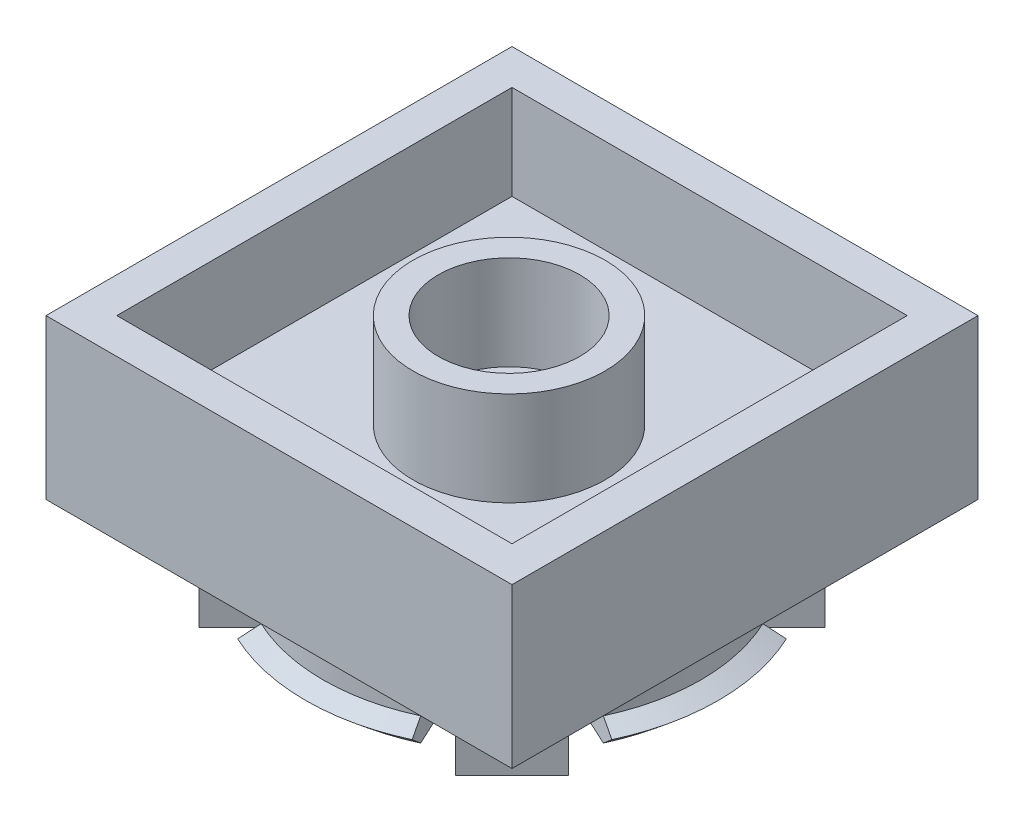
SolidWorks part; units mm, degrees
ref_plane "Front Plane" through (0, 0, 0) normal (0, 0, 1) x (1, 0, 0)
ref_plane "Top Plane" through (0, 0, 0) normal (0, 1, 0) x (1, 0, 0)
ref_plane "Right Plane" through (0, 0, 0) normal (1, 0, 0) x (0, 0, -1)
sketch "Sketch2" plane through (0, 0, 0) normal (0, 1, 0) x (1, 0, 0)
  line L1 (0, 0) -> (15.8, 0)
  line L2 (0, 0) -> (0, 15.8)
  line L3 (0, 15.8) -> (15.8, 15.8)
  line L4 (15.8, 0) -> (15.8, 15.8)
  dimension "D1" = 15.8
  dimension "D2" = 15.8
extrude "Boss-Extrude2" add sketch "Sketch2" against normal blind 5.4
sketch "Sketch4" plane through (0, 0, 0) normal (0, 1, 0) x (1, 0, 0)
  line L0 (15.8, 0) -> (15.8, 15.8) construction
  line L1 (14.6, 14.6) -> (1.2, 14.6)
  line L2 (14.6, 14.6) -> (14.6, 1.2)
  line L3 (14.6, 1.2) -> (1.2, 1.2)
  line L4 (1.2, 14.6) -> (1.2, 1.2)
  line L5 (0, -55) -> (0, 55) construction
  line L6 (-55, 0) -> (55, 0) construction
  line L7 (15.8, 15.8) -> (0, 15.8) construction
  dimension "D1" = 1.2
  dimension "D2" = 1.2
  dimension "D3" = 1.2
  dimension "D4" = 1.2
extrude "Cut-Extrude1" cut sketch "Sketch4" against normal offset from surface (3.2 mm away) 2.2 up to face at (7.9, -5.4, -7.9)
sketch "Sketch7" plane through (0, -3.2, 0) normal (0, 1, 0) x (1, 0, 0)
  line L0 (15.8, 0) -> (15.8, 15.8) construction
  line L1 (15.8, 15.8) -> (0, 15.8) construction
  circle A0 centre (7.85, 7.85) radius 3.255
  circle A1 centre (7.85, 7.85) radius 2.4
  dimension "D1" = 6.51
  dimension "D2" = 4.8
  dimension "D3" = 7.95
  dimension "D4" = 7.95
extrude "Boss-Extrude5" add sketch "Sketch7" along normal up to surface (3.2 mm away) up to face at (7.9, 0, -7.9)
sketch "Sketch8" plane through (0, -5.4, 0) normal (0, -1, 0) x (-1, 0, 0)
  line L0 (-15.8, 0) -> (-15.8, 15.8) construction
  line L1 (-15.8, 15.8) -> (0, 15.8) construction
  circle A0 centre (-7.9, 7.9) radius 5.15
  dimension "D1" = 10.3
  dimension "D2" = 7.9
  dimension "D3" = 7.9
extrude "Cut-Extrude2" cut sketch "Sketch8" against normal blind 0.3
sketch "Sketch11" plane through (0, -5.4, 0) normal (0, -1, 0) x (1, 0, 0)
  line L2 (7.9, -7.9) -> (15.8, 0)
  line L3 (2.97, 0) -> (-2.97, 0) construction
  line L4 (11.683, -2.2078) -> (13.5922, -4.117)
  line L5 (13.5922, -4.117) -> (11.683, -2.2078)
  line L6 (13.5922, -4.117) -> (14.1579, -3.5513)
  line L7 (11.683, -2.2078) -> (12.2487, -1.6421)
  line L8 (14.1579, -3.5513) -> (12.2487, -1.6421)
  line L9 (11.683, -2.2078) -> (10.4597, -3.4311)
  line L10 (13.5922, -4.117) -> (12.3689, -5.3403)
  circle A0 centre (7.9, -7.9) radius 6.7
  circle A1 centre (7.9, -7.9) radius 5.15 construction
  point P9 (12.6376, -3.1624)
  circle M6 centre (7.9, -7.9) radius 5.15
  dimension "D1" = 13.4
  dimension "D2" = 2.7
  dimension "D3" = 0.8
extrude "Boss-Extrude8" add sketch "Sketch11" along normal blind 2.8 contours L2 L8 L7 L4 | A0 L4 L9 | L2 A0 L9 M6 | L10 A0 L2 M6 | A0 L10 L4 | L6 L8 L2 L4 region at (11.5727, -5.4, -3.2684) region at (12.5316, -5.4, -4.2273) region at (12.4432, -5.4, -2.4022) region at (11.8921, -5.4, -2.475) region at (13.3978, -5.4, -3.3568) region at (13.325, -5.4, -3.9079)
ref_axis "Axis1" through (7.9, -5.1, -7.9) along (0, -1, 0)
pattern_circular "CirPattern1" count 4 over 360 about axis through (7.9, -5.1, -7.9) along (0, -1, 0) of "Boss-Extrude8"
sketch "Sketch12" plane through (0, -5.4, 0) normal (0, -1, 0) x (1, 0, 0)
  line L0 (7.9, -7.9) -> (15.8, -7.9)
  line L1 (15.8, 0) -> (15.8, -15.8) construction
  line L2 (13.3, -7.9) -> (14.3, -7.9)
  line L3 (13.7004, -5.1952) -> (12.7941, -5.6179)
  line L4 (13.7004, -10.6048) -> (12.7941, -10.1821)
  line L5 (10.6048, -13.7004) -> (10.1821, -12.7941)
  line L6 (5.1952, -13.7004) -> (5.6179, -12.7941)
  line L7 (2.0996, -10.6048) -> (3.0059, -10.1821)
  line L8 (2.0996, -5.1952) -> (3.0059, -5.6179)
  line L9 (5.1952, -2.0996) -> (5.6179, -3.0059)
  line L10 (10.6048, -2.0996) -> (10.1821, -3.0059)
  arc A0 (13.7004, -10.6048) -> (13.7004, -5.1952) centre (7.9, -7.9) ccw
  arc A1 (12.7941, -10.1821) -> (12.7941, -5.6179) centre (7.9, -7.9) ccw
  arc A2 (5.6179, -12.7941) -> (10.1821, -12.7941) centre (7.9, -7.9) ccw
  arc A3 (5.1952, -13.7004) -> (10.6048, -13.7004) centre (7.9, -7.9) ccw
  arc A4 (3.0059, -5.6179) -> (3.0059, -10.1821) centre (7.9, -7.9) ccw
  arc A5 (2.0996, -5.1952) -> (2.0996, -10.6048) centre (7.9, -7.9) ccw
  arc A6 (10.1821, -3.0059) -> (5.6179, -3.0059) centre (7.9, -7.9) ccw
  arc A7 (10.6048, -2.0996) -> (5.1952, -2.0996) centre (7.9, -7.9) ccw
  point P27 (7.9, -7.9)
  dimension "D2" = 1
  dimension "D1" = 4
extrude "Boss-Extrude9" add sketch "Sketch12" along normal blind 2.9 contours A1 L0 A0 L3 | A1 L3 A0 L4 | L9 A6 L10 A7 | L5 A2 L6 A3 | L7 A4 L8 A5 region at (13.6282, -5.4, -6.6301)
sketch "Sketch26" plane through (4.4369, 0, -9.5149) normal (-0.4226, 0, 0.9063) x (0.9063, 0, 0.4226)
  line L0 (10.2211, -7.5) -> (10.8211, -7.8)
  line L1 (10.2211, -8.3) -> (10.2211, -5.4) construction
  line L2 (10.8211, -7.8) -> (10.2211, -8.3)
  line L3 (10.2211, -8.3) -> (10.2211, -7.5)
  dimension "D1" = 2.1
  dimension "D2" = 2.4
  dimension "D3" = 0.6
revolve "Revolve4" add sketch "Sketch26" angle 50 about axis through (7.9, -5.1, -7.9) along (0, -1, 0) reverse direction yes
pattern_circular "CirPattern9" count 4 every 90 about axis through (7.9, -5.1, -7.9) along (0, -1, 0) of "Revolve4"
ref_plane "Plane2" through (0, 0, -7.9) normal (0, 0, -1) x (-1, 0, 0)
